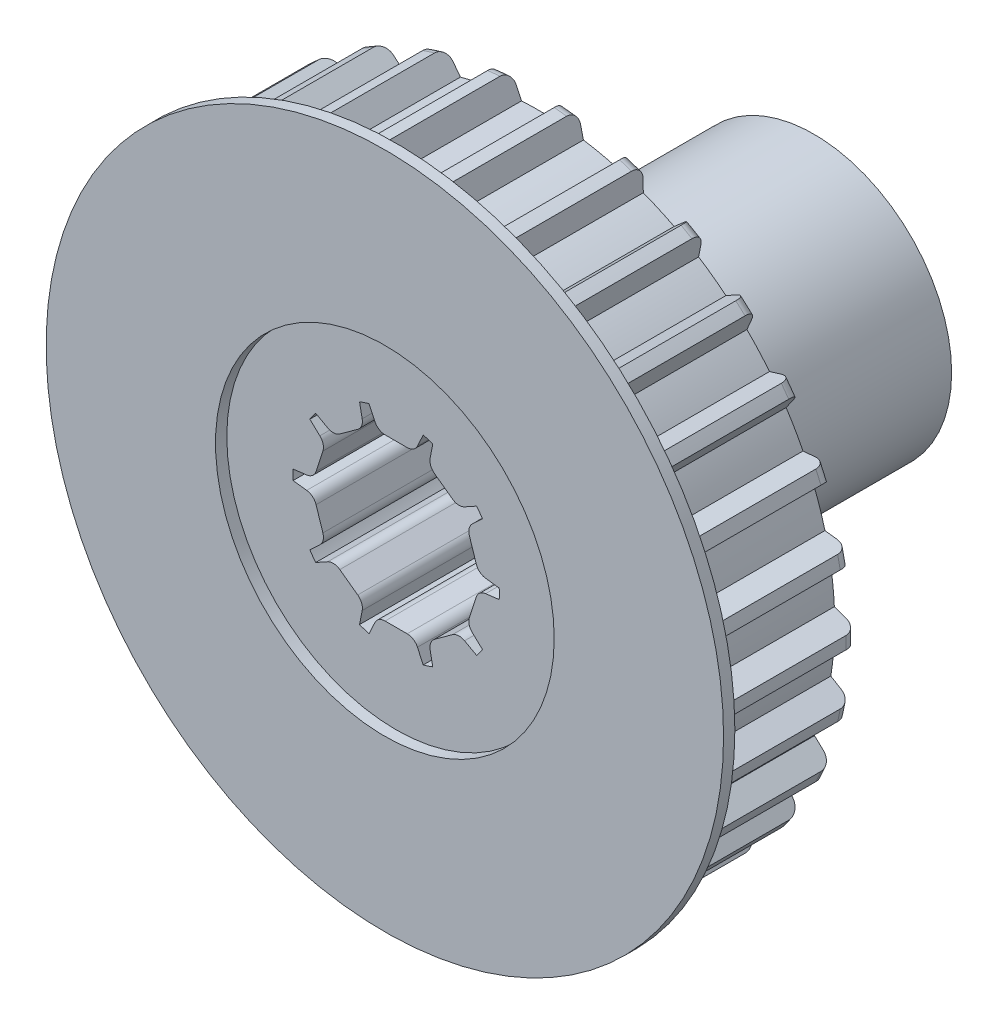
SolidWorks part; units mm, degrees
material "PMMA"
ref_plane "Ebene vorne" through (0, 0, 0) normal (0, 0, 1) x (1, 0, 0)
ref_plane "Ebene oben" through (0, 0, 0) normal (0, 1, 0) x (1, 0, 0)
ref_plane "Ebene rechts" through (0, 0, 0) normal (1, 0, 0) x (0, 0, -1)
ref_axis "Achse1" through (0, 0, 0.8815) along (0, 0, -1)
sketch "Skizze1" plane through (0, 0, 0) normal (1, 0, 0) x (0, 0, -1)
  line L0 (0, 31.7827) -> (0, -32.6712) construction
  line L1 (-33.2769, 0) -> (37.2346, 0) construction
  line L2 (0, 4.57) -> (0, 14.12)
  line L3 (0, 14.12) -> (5.8, 14.12)
  line L4 (6.3, 13.62) -> (6.3, 6.1)
  line L6 (19.3, 6.1) -> (19.3, 4.57)
  line L7 (19.3, 4.57) -> (0, 4.57)
  line L8 (19.3, 6.1) -> (6.3, 6.1)
  arc A1 (5.8, 14.12) -> (6.3, 13.62) centre (5.8, 13.62) cw
  point P19 (6.3, 14.12)
  dimension "D8" = 0.5
  dimension "D1" = 6.3
  dimension "D2" = 28.24
  dimension "D3" = 13
  dimension "D5" = 6.1
  dimension "D7" = 9.14
revolve "Rotation1" add sketch "Skizze1" angle 360 about L1
sketch "Skizze2" plane through (0, 0, 0) normal (0, 0, 1) x (1, 0, 0)
  line L0 (0, 25.2337) -> (0, -18.8875) construction
  line L1 (18.5217, 0) -> (-21.6513, 0) construction
  line L2 (0.7476, 13.0987) -> (1.2, 14.0689)
  line L3 (-0.7476, 13.0987) -> (-1.2, 14.0689)
  circle A0 centre (0, 0) radius 14.12 construction
  circle A1 centre (0, 0) radius 13.12 construction
  circle A2 centre (0, 0) radius 14.12 construction
  arc A3 (0.7476, 13.0987) -> (-0.7476, 13.0987) centre (0, 0) ccw
  arc A4 (1.2, 14.0689) -> (-1.2, 14.0689) centre (0, 0) ccw
  dimension "D1" = 26.24
  dimension "D2" = 50
  dimension "D3" = 2.4
  dimension "D4" = 1.4951
extrude "Schnitt-Linear austragen1" cut sketch "Skizze2" against normal through all
pattern_circular "Kreismuster1" count 30 over 360 about axis through (0, 0, 0.8815) along (0, 0, -1) of "Schnitt-Linear austragen1"
sketch "Skizze3" plane through (0, 0, 0) normal (0, 0, 1) x (1, 0, 0)
  line L0 (0, 18.7184) -> (0, -16.4301) construction
  line L1 (17.9538, 0) -> (-20.4113, 0) construction
  line L2 (0.8085, 3.57) -> (1.2, 4.4096)
  line L3 (-0.8085, 3.57) -> (-1.2, 4.4096)
  line L4 (0.8085, 3.57) -> (-0.8085, 3.57)
  line L5 (-2.5176, 4.57) -> (3.1687, 4.57) construction
  circle A0 centre (0, 0) radius 4.57 construction
  circle A2 centre (0, 0) radius 4.57 construction
  arc A3 (1.2, 4.4096) -> (-1.2, 4.4096) centre (0, 0) ccw
  dimension "D1" = 9.14
  dimension "D2" = 1
  dimension "D3" = 50
  dimension "D4" = 2.4
  dimension "D5" = 1.6169
extrude "Aufsatz-Linear austragen1" add sketch "Skizze3" against normal up to surface (19.3 mm away) up to face at (6.1, 0, -19.3)
fillet "Verrundung1" radius 0.5 2 edges at (0.8085, 3.57, -9.65) (-0.8085, 3.57, -9.65)
pattern_circular "Kreismuster2" count 10 over 360 about axis through (0, 0, 0.8815) along (0, 0, -1) of "Aufsatz-Linear austragen1", "Verrundung1"
sketch "Skizze4" plane through (0, 0, 0) normal (1, 0, 0) x (0, 0, -1)
  line L0 (0, 19.3542) -> (0, -18.0091) construction
  line L1 (-12.7482, 0) -> (17.6163, 0) construction
  line L2 (0, 7.5) -> (-0.5, 7.5)
  line L3 (-0.5, 7.5) -> (-0.5, 15)
  line L4 (-0.5, 15) -> (0, 15)
  line L5 (0, 15) -> (0, 14.25)
  line L6 (0, 14.25) -> (0.6536, 13.5964)
  line L7 (0.8, 13.2429) -> (0.8, 13)
  line L8 (0.8, 13) -> (0, 13)
  line L9 (0, 13) -> (0, 7.5)
  arc A0 (0.8, 13.2429) -> (0.6536, 13.5964) centre (0.3, 13.2429) ccw
  dimension "D8" = 0.5
  dimension "D1" = 15
  dimension "D2" = 0.5
  dimension "D3" = 30
  dimension "D4" = 14.25
  dimension "D5" = 45
  dimension "D6" = 0.8
  dimension "D7" = 13
revolve "Rotation2" add sketch "Skizze4" angle 360 about L1
sketch "Skizze5" plane through (0, 0, 0) normal (1, 0, 0) x (0, 0, -1)
  line L0 (13.5237, 0) -> (-4.1574, 0) construction
  line L1 (0, -18.0539) -> (0, 17.4561) construction
  line L2 (19.3, 4.2) -> (18.5, 5)
  line L3 (18.5, 5) -> (18.5, 6.1)
  line L4 (18.5, 6.1) -> (19.3, 6.1)
  line L5 (19.3, 6.1) -> (19.3, 4.2)
  line L7 (19.3, -6.1) -> (19.3, 6.1) construction
  line L8 (19.3, 6.1) -> (6.3, 6.1) construction
  dimension "D1" = 135
  dimension "D2" = 5
  dimension "D3" = 0.8
revolve "Schnitt-Rotation1" cut sketch "Skizze5" angle 360 about L0
fillet "Verrundung2" radius 0.5 10 edges at (2.4687, 3.3979, -19.3) (0, 4.2, -19.3) (-2.4687, 3.3979, -19.3) (-3.9944, 1.2979, -19.3) (-3.9944, -1.2979, -19.3) (-2.4687, -3.3979, -19.3) (3.9944, 1.2979, -19.3) (3.9944, -1.2979, -19.3) (2.4687, -3.3979, -19.3) (0, -4.2, -19.3)
